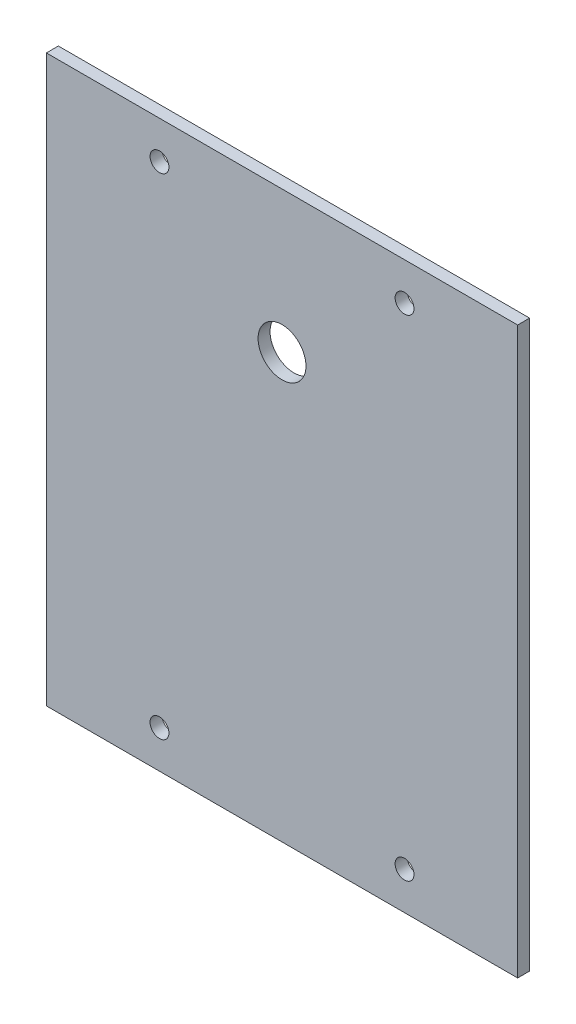
SolidWorks part; units mm, degrees
material "Custom Plastic"
ref_plane "Front Plane" through (0, 0, 0) normal (0, 0, 1) x (1, 0, 0)
ref_plane "Top Plane" through (0, 0, 0) normal (0, 1, 0) x (1, 0, 0)
ref_plane "Right Plane" through (0, 0, 0) normal (1, 0, 0) x (0, 0, -1)
sketch "Sketch1" plane through (0, 0, 0) normal (0, 0, 1) x (1, 0, 0)
  line L1 (-125, 150) -> (0, 150)
  line L2 (-125, 150) -> (-125, 0)
  line L3 (-125, 0) -> (0, 0)
  line L4 (0, 150) -> (0, 0)
  dimension "D1" = 150
  dimension "D2" = 125
extrude "Boss-Extrude1" add sketch "Sketch1" along normal blind 3.175
sketch "Sketch2" plane through (0, 0, 3.175) normal (0, 0, 1) x (1, 0, 0)
  line L0 (-125, 150) -> (-125, 0) construction
  line L1 (0, 0) -> (0, 150) construction
  line L2 (0, 150) -> (-125, 150) construction
  circle A0 centre (-95, 140) radius 2.5
  circle A1 centre (-30, 140) radius 2.5
  dimension "D1" = 5
  dimension "D2" = 5
  dimension "D3" = 30
  dimension "D4" = 30
  dimension "D5" = 10
  dimension "D6" = 10
extrude "Cut-Extrude1" cut sketch "Sketch2" against normal up to surface (3.175 mm away) up to face at (-62.5, 75, 0)
ref_plane "Plane1" through (0, 75, 0) normal (0, 1, 0) x (1, 0, 0)
mirror "Mirror1" about plane through (0, 75, 0) normal (0, 1, 0) of "Cut-Extrude1"
sketch "Sketch3" plane through (0, 0, 3.175) normal (0, 0, 1) x (1, 0, 0)
  line L2 (-62.5, 150) -> (-62.5, 0) construction
  line L3 (0, 150) -> (-125, 150) construction
  line L4 (-125, 0) -> (0, 0) construction
  line L5 (-125, 75) -> (0, 75) construction
  line L6 (-125, 150) -> (-125, 0) construction
  line L7 (0, 0) -> (0, 150) construction
  circle A1 centre (-62.5, 112.5) radius 6.35
  dimension "D1" = 37.5
  dimension "D2" = 12.7
extrude "Cut-Extrude2" cut sketch "Sketch3" against normal up to surface (3.175 mm away) up to face at (-92.5, 10, 0)
